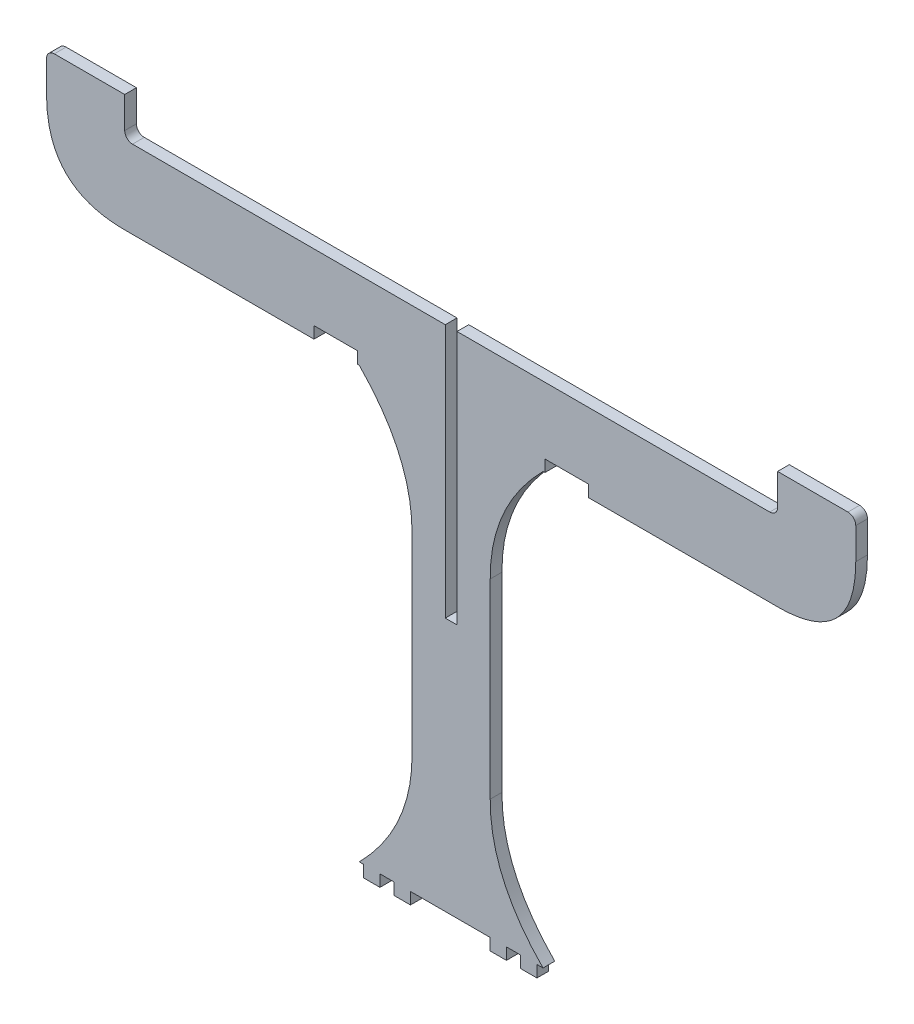
SolidWorks part; units mm, degrees
ref_plane "Přední rovina" through (0, 0, 0) normal (0, 0, 1) x (1, 0, 0)
ref_plane "Horní rovina" through (0, 0, 0) normal (0, 1, 0) x (1, 0, 0)
ref_plane "Pravá rovina" through (0, 0, 0) normal (1, 0, 0) x (0, 0, -1)
sketch "Skica1" plane through (0, 0, 0) normal (0, 0, 1) x (1, 0, 0)
  line L0 (-30.6426, 2.6943) -> (16.3574, 2.6943)
  line L1 (-7.1426, 2.6943) -> (-7.1426, -107.3057)
  line L2 (16.3574, -107.3057) -> (-30.6426, -107.3057)
  line L3 (-17.1426, 9.0001) -> (-17.1426, -176.0586) construction
  line L4 (27.2473, -27.3057) -> (-64.2445, -27.3057) construction
  line L5 (15.3668, -77.3057) -> (-64.2445, -77.3057) construction
  line L6 (-17.1426, -27.8784) -> (-17.1426, -76.656)
  line L7 (2.8574, -27.8784) -> (2.8574, -76.656)
  line L24 (-7.1426, -15.139) -> (-7.1426, 72.526) construction
  line L25 (10.652, -107.3057) -> (10.652, -110.3057)
  line L26 (10.652, -107.3057) -> (14.802, -107.3057)
  line L27 (14.802, -107.3057) -> (14.802, -110.3057)
  line L28 (10.652, -110.3057) -> (14.802, -110.3057)
  line L29 (2.852, -107.3057) -> (2.852, -110.3057)
  line L30 (2.852, -107.3057) -> (7.002, -107.3057)
  line L31 (7.002, -107.3057) -> (7.002, -110.3057)
  line L32 (2.852, -110.3057) -> (7.002, -110.3057)
  line L33 (-25.348, -110.3057) -> (-29.498, -110.3057)
  line L34 (-29.498, -107.3057) -> (-29.498, -110.3057)
  line L35 (-25.348, -107.3057) -> (-29.498, -107.3057)
  line L36 (-25.348, -107.3057) -> (-25.348, -110.3057)
  line L37 (-17.548, -110.3057) -> (-21.698, -110.3057)
  line L38 (-21.698, -107.3057) -> (-21.698, -110.3057)
  line L39 (-17.548, -107.3057) -> (-21.698, -107.3057)
  line L40 (-17.548, -107.3057) -> (-17.548, -110.3057)
  line L41 (-190.6426, 2.6943) -> (100.2644, 2.6943) construction
  line L42 (16.3574, 2.6943) -> (16.3574, 73.8241) construction
  line L43 (-30.6426, 73.8241) -> (-30.6426, 2.6943) construction
  line L44 (-110.6426, 2.6943) -> (-110.6426, 52.9232) construction
  line L45 (-190.6426, 32.6943) -> (86.9117, 32.6943) construction
  line L46 (-30.6426, 2.6943) -> (-90.6426, 2.6943)
  line L47 (-90.6426, -13.7924) -> (-90.6426, 96.8534) construction
  line L48 (-70.6426, -7.8313) -> (-70.6426, 84.4343) construction
  line L49 (-194.5635, 22.6943) -> (-7.1426, 22.6943) construction
  line L50 (-108.6426, 32.6943) -> (-90.6426, 32.6943)
  line L51 (-90.6426, 32.6943) -> (-90.6426, 24.6943)
  line L52 (-110.6426, 22.6943) -> (-110.6426, 30.6943)
  line L53 (16.3574, 2.6943) -> (76.3574, 2.6943)
  line L54 (-110.6426, 22.6943) -> (-110.6426, 2.6943) construction
  line L55 (76.3574, 32.6943) -> (76.3574, 24.6943)
  line L56 (-110.6426, 2.6943) -> (-90.6426, 2.6943) construction
  line L57 (94.3574, 32.6943) -> (76.3574, 32.6943)
  line L58 (-88.6426, 22.6943) -> (74.3574, 22.6943)
  line L59 (-7.1426, 22.6943) -> (-7.1426, 2.6943)
  line L60 (96.3574, 22.6943) -> (96.3574, 30.6943)
  line L61 (96.3574, 22.6943) -> (96.3574, 2.6943) construction
  line L62 (96.3574, 2.6943) -> (76.3574, 2.6943) construction
  arc A0 (74.3574, 22.6943) -> (76.3574, 24.6943) centre (74.3574, 24.6943) ccw
  arc A1 (-88.6426, 22.6943) -> (-90.6426, 24.6943) centre (-88.6426, 24.6943) cw
  arc A2 (-110.6426, 30.6943) -> (-108.6426, 32.6943) centre (-108.6426, 30.6943) cw
  arc A3 (96.3574, 30.6943) -> (94.3574, 32.6943) centre (94.3574, 30.6943) ccw
  spline S0 degree 2 poles (-30.6426, 2.6943) (-17.0251, -11.1181) (-17.1426, -27.8784) knots 0 0 0 1 1 1
  spline S1 degree 2 poles (-30.6426, -107.3057) (-17.0093, -93.4583) (-17.1426, -76.656) knots 0 0 0 1 1 1
  spline S2 degree 2 poles (16.3574, 2.6943) (2.7399, -11.1181) (2.8574, -27.8784) knots 0 0 0 1 1 1
  spline S3 degree 2 poles (16.3574, -107.3057) (2.724, -93.4583) (2.8574, -76.656) knots 0 0 0 1 1 1
  spline S4 degree 2 poles (-110.6426, 22.6943) (-110.6426, 2.6943) (-90.6426, 2.6943) knots 0 0 0 1 1 1
  spline S5 degree 2 poles (96.3574, 22.6943) (96.3574, 2.6943) (76.3574, 2.6943) knots 0 0 0 1 1 1
  point P29 (0, 0)
  point P37 (-110.6426, 22.6943)
  point P54 (-110.6426, 32.6943)
  point P55 (-90.6426, 32.6943)
  point P56 (-90.6426, 22.6943)
  point P70 (-90.6426, 22.6943)
  point P73 (-110.6426, 32.6943)
  dimension "D15" = 60
  dimension "D17" = 2
  dimension "D18" = 2
  dimension "D1" = 110
  dimension "D2" = 23.5
  dimension "D3" = 30
  dimension "D4" = 30
  dimension "D5" = 30.6498
  dimension "D6" = 23.5
  dimension "D7" = 47
  dimension "D8" = 30
  dimension "D9" = 30
  dimension "D10" = 10
  dimension "D11" = 80
  dimension "D12" = 20
  dimension "D13" = 40
  dimension "D14" = 10
  dimension "D16" = 10
  dimension "D19" = 103.5
  dimension "D20" = 103.5
extrude "Přidat vysunutím2" add sketch "Skica1" along normal blind 3 contours S1 L2 L1 L0 S0 L6 | L2 S3 L7 S2 L0 L1 | L0 | L0 | L0 | L0 | L40 L2 L38 L37 | L36 L2 L34 L33 | L29 L32 L31 L2 | L25 L28 L27 L2 region at (-61.2298, 14.2338, 0) region at (-13.8581, -52.3107, 0) region at (46.9445, 14.2338, 0) region at (-0.4272, -52.3107, 0) region at (4.927, -108.8057, 0) region at (-19.623, -108.8057, 0) region at (-27.423, -108.8057, 0) region at (12.727, -108.8057, 0)
sketch "Skica4" plane through (0, 0, 0) normal (0, 0, -1) x (-1, 0, 0)
  line L0 (7.1426, -117.242) -> (7.1426, 117.242) construction
  line L1 (-2.8574, -27.8784) -> (-2.8574, -76.656) construction
  line L2 (17.1426, -27.8784) -> (17.1426, -76.656) construction
  line L3 (88.6426, 22.6943) -> (-74.3574, 22.6943) construction
  line L4 (8.6426, 22.6943) -> (5.6426, 22.6943)
  line L5 (8.6426, 22.6943) -> (8.6426, -42.3057)
  line L6 (8.6426, -42.3057) -> (5.6426, -42.3057)
  line L7 (5.6426, 22.6943) -> (5.6426, -42.3057)
  line L8 (8.6426, 22.6943) -> (5.6426, -42.3057) construction
  line L9 (8.6426, -42.3057) -> (5.6426, 22.6943) construction
  line L10 (71.2987, 0) -> (-57.0134, 0) construction
  line L12 (42.2226, 5.6943) -> (31.1426, 5.6943)
  line L13 (42.2226, 5.6943) -> (42.2226, -5.6943)
  line L14 (42.2226, -5.6943) -> (31.1426, -5.6943)
  line L15 (31.1426, 5.6943) -> (31.1426, -5.6943)
  line L16 (42.2226, 5.6943) -> (31.1426, -5.6943) construction
  line L17 (42.2226, -5.6943) -> (31.1426, 5.6943) construction
  line L18 (30.6426, 2.6943) -> (90.6426, 2.6943) construction
  line L19 (-27.9374, 5.6943) -> (-16.8574, -5.6943) construction
  line L20 (-27.9374, -5.6943) -> (-16.8574, 5.6943) construction
  line L21 (-27.9374, -5.6943) -> (-16.8574, -5.6943)
  line L22 (-16.8574, 5.6943) -> (-16.8574, -5.6943)
  line L23 (-27.9374, 5.6943) -> (-16.8574, 5.6943)
  line L24 (-27.9374, 5.6943) -> (-27.9374, -5.6943)
  point P6 (7.1426, -9.8057)
  point P11 (7.1426, 0)
  point P14 (36.6826, 0)
  point P24 (31.1426, 3.7753)
  point P25 (-22.3974, 0)
  point P27 (31.1426, 2.97)
  dimension "D1" = 10
  dimension "D2" = 10
  dimension "D3" = 65
  dimension "D4" = 3
  dimension "D5" = 24
  dimension "D6" = 3
  dimension "D7" = 0.5
  dimension "D8" = 0.5
  dimension "D9" = 11.08
  dimension "D10" = 11.08
extrude "Odebrat vysunutím2" cut sketch "Skica4" against normal blind 3
